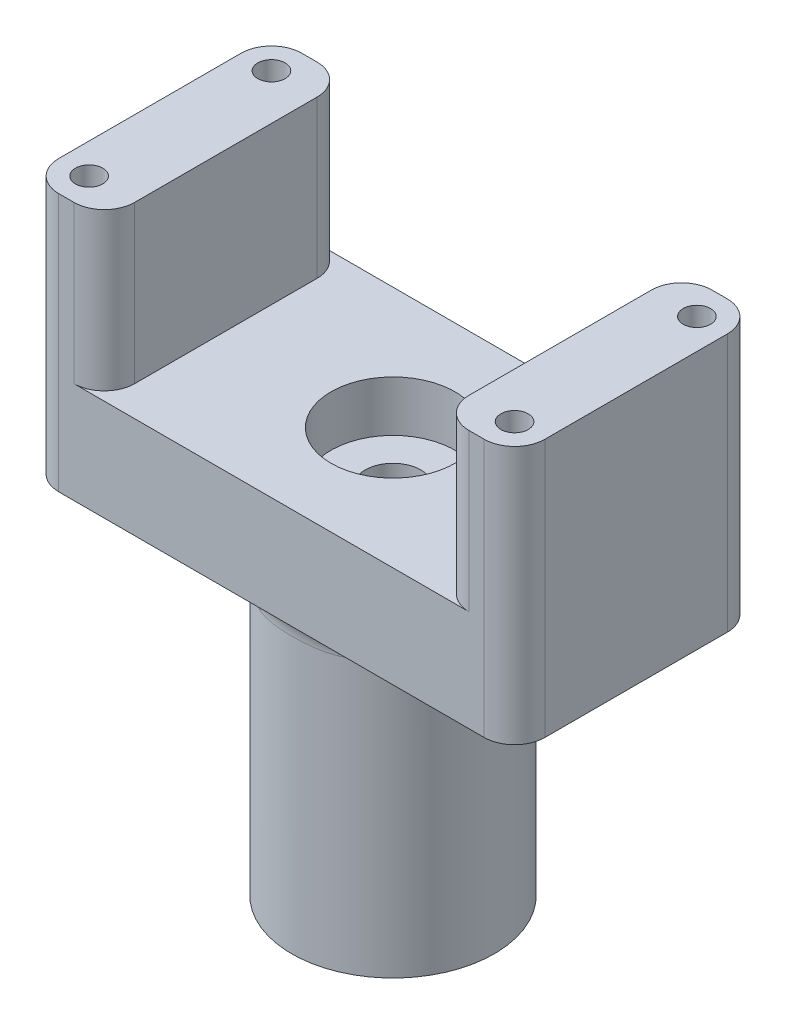
SolidWorks part; units mm, degrees
material "Nylon 101"
ref_plane "Front Plane" through (0, 0, 0) normal (0, 0, 1) x (1, 0, 0)
ref_plane "Top Plane" through (0, 0, 0) normal (0, 1, 0) x (1, 0, 0)
ref_plane "Right Plane" through (0, 0, 0) normal (1, 0, 0) x (0, 0, -1)
sketch "Sketch1" plane through (0, 0, 0) normal (0, 1, 0) x (1, 0, 0)
  line L0 (-21, -9) -> (21, 9) construction
  line L1 (19, 12) -> (16.5, 12)
  line L2 (16.5, 12) -> (16.5, -12)
  line L3 (16.5, -12) -> (19, -12)
  line L4 (0, -55) -> (0, 55) construction
  line L5 (-16.5, -12) -> (-19, -12)
  line L6 (-16.5, 12) -> (-16.5, -12)
  line L7 (-19, 12) -> (-16.5, 12)
  point P2 (0, 0)
  line B0 (-15.5, -16.5) -> (15.5, -16.5)
  line B1 (16.5, -15.5) -> (16.5, -14.5)
  line B2 (19, -12) -> (21, -12)
  line B3 (24, -9) -> (24, 9)
  line B4 (21, 12) -> (19, 12)
  line B5 (16.5, 14.5) -> (16.5, 15.5)
  line B6 (15.5, 16.5) -> (-15.5, 16.5)
  line B7 (-16.5, 15.5) -> (-16.5, 14.5)
  line B8 (-19, 12) -> (-21, 12)
  line B9 (-24, 9) -> (-24, -9)
  line B10 (-21, -12) -> (-19, -12)
  line B11 (-16.5, -14.5) -> (-16.5, -15.5)
  circle B12 centre (21, 9) radius 1.35
  circle B13 centre (-21, 9) radius 1.35
  circle B14 centre (21, -9) radius 1.35
  circle B15 centre (-21, -9) radius 1.35
  arc B16 (15.5, -16.5) -> (16.5, -15.5) centre (15.5, -15.5) ccw
  arc B17 (19, -12) -> (16.5, -14.5) centre (19, -14.5) ccw
  arc B18 (21, -12) -> (24, -9) centre (21, -9) ccw
  arc B19 (24, 9) -> (21, 12) centre (21, 9) ccw
  arc B20 (16.5, 14.5) -> (19, 12) centre (19, 14.5) ccw
  arc B21 (16.5, 15.5) -> (15.5, 16.5) centre (15.5, 15.5) ccw
  arc B22 (-15.5, 16.5) -> (-16.5, 15.5) centre (-15.5, 15.5) ccw
  arc B23 (-19, 12) -> (-16.5, 14.5) centre (-19, 14.5) ccw
  arc B24 (-21, 12) -> (-24, 9) centre (-21, 9) ccw
  arc B25 (-24, -9) -> (-21, -12) centre (-21, -9) ccw
  arc B26 (-16.5, -14.5) -> (-19, -12) centre (-19, -14.5) ccw
  arc B27 (-16.5, -15.5) -> (-15.5, -16.5) centre (-15.5, -15.5) ccw
sketch_block_instance "Block-piCAM-1"
sketch_block "Block-piCAM"
extrude "Boss-Extrude1" add sketch "Sketch1" along normal blind 15.5 contours B15 L6 L7 B8 B24 B9 B25 B10 L5 B13 | B3 B19 B4 L1 L2 B12 L3 B2 B18 B14 region at (20.1256, 0, 0) region at (-20.1256, 0, 0)
sketch "Sketch2" plane through (0, 0, 0) normal (0, 1, 0) x (1, 0, 0)
  line L0 (24, 9) -> (24, -9) construction
  line L1 (21, -12) -> (16.5, -12) construction
  line L3 (16.5, 12) -> (21, 12) construction
  line L4 (-16.5, -12) -> (-21, -12) construction
  line L5 (-24, -9) -> (-24, 9) construction
  line L6 (-21, 12) -> (-16.5, 12) construction
  line L8 (24, 9) -> (24, -9)
  line L9 (21, -12) -> (16.5, -12)
  line L11 (16.5, 12) -> (21, 12)
  line L12 (-16.5, -12) -> (-21, -12)
  line L13 (-24, -9) -> (-24, 9)
  line L14 (-21, 12) -> (-16.5, 12)
  line L16 (-16.5, -12) -> (16.5, -12)
  line L17 (-16.5, 12) -> (16.5, 12)
  arc A0 (21, -12) -> (24, -9) centre (21, -9) ccw construction
  arc A1 (24, 9) -> (21, 12) centre (21, 9) ccw construction
  arc A2 (-24, -9) -> (-21, -12) centre (-21, -9) ccw construction
  arc A3 (-21, 12) -> (-24, 9) centre (-21, 9) ccw construction
  circle A4 centre (21, 9) radius 1.35 construction
  circle A5 centre (21, -9) radius 1.35 construction
  circle A6 centre (-21, 9) radius 1.35 construction
  circle A7 centre (-21, -9) radius 1.35 construction
  arc A8 (21, -12) -> (24, -9) centre (21, -9) ccw
  arc A9 (24, 9) -> (21, 12) centre (21, 9) ccw
  arc A10 (-24, -9) -> (-21, -12) centre (-21, -9) ccw
  arc A11 (-21, 12) -> (-24, 9) centre (-21, 9) ccw
  circle A12 centre (21, 9) radius 1.35
  circle A13 centre (21, -9) radius 1.35
  circle A14 centre (-21, 9) radius 1.35
  circle A15 centre (-21, -9) radius 1.35
extrude "Boss-Extrude2" add sketch "Sketch2" against normal blind 10
sketch "Sketch4" plane through (0, -10, 0) normal (0, -1, 0) x (1, 0, 0)
  circle A0 centre (0, 0) radius 10
  dimension "D1" = 20
extrude "Boss-Extrude3" add sketch "Sketch4" along normal blind 30
hole_wizard "CBORE for M5 Hex Head Bolt1" positions "3DSketch2" profile "Sketch3" counterbore size "M5" standard "ANSI Metric" end condition through all
sketch3d "3DSketch2"
  point P0 (0, 0, 0)
  point P3 (0, 0, 0)
sketch "Sketch3" plane through (0, 0, 0) normal (1, 0, 0) x (0, 0, 1)
  line L0 (0, 0) -> (0, 40)
  line L1 (0, 40) -> (2.75, 40)
  line L3 (2.75, 40) -> (2.75, 5)
  line L4 (2.75, 5) -> (6.12, 5)
  line L5 (6.12, 5) -> (6.12, 0)
  line L7 (6.12, 0) -> (0, 0)
  line L11 (0, -6.35) -> (0, 107.95) construction
  dimension "Thru Hole Dia." = 5.5
  dimension "Thru Hole Depth" = 40
  dimension "C'Bore Dia." = 12.24
  dimension "C'Bore Depth" = 5
fillet "Fillet1" radius 3 5 edges at (16.5, 7.75, -12) (16.5, 7.75, 12) (-16.5, 7.75, -12) (-16.5, 7.75, 12) (0, -10, 10)
